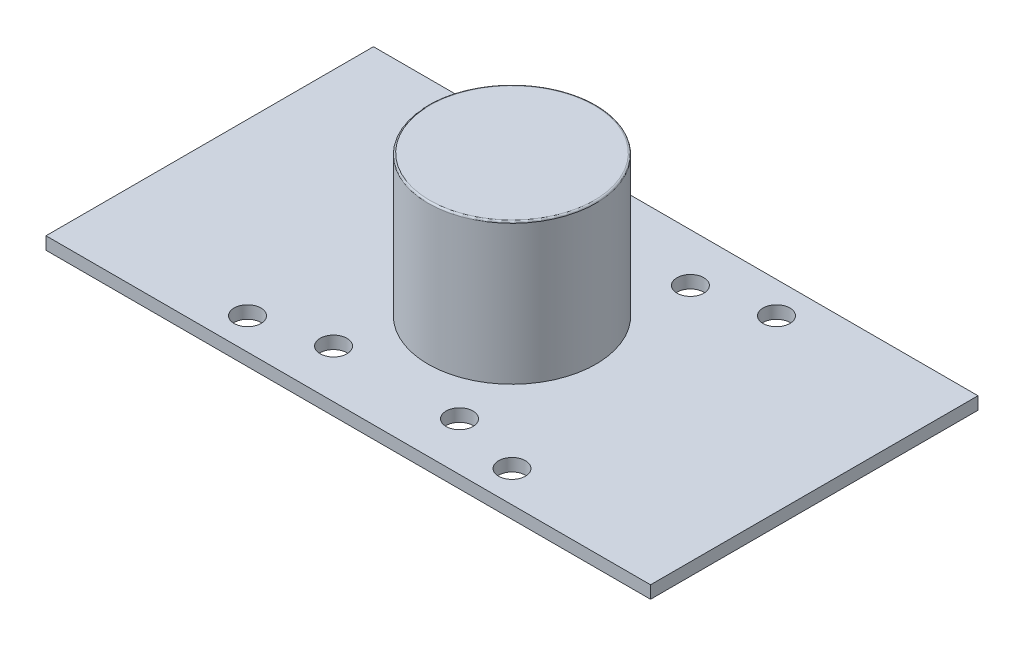
SolidWorks part; units mm, degrees
ref_plane "Front Plane" through (0, 0, 0) normal (0, 0, 1) x (1, 0, 0)
ref_plane "Top Plane" through (0, 0, 0) normal (0, 1, 0) x (1, 0, 0)
ref_plane "Right Plane" through (0, 0, 0) normal (1, 0, 0) x (0, 0, -1)
sketch "Sketch1" plane through (0, 0, 0) normal (0, 1, 0) x (1, 0, 0)
  line L0 (0, 0) -> (72, 0)
  line L1 (72, 0) -> (72, 39)
  line L2 (72, 39) -> (0, 39)
  line L3 (0, 39) -> (0, 0)
extrude "Boss-Extrude1" add sketch "Sketch1" along normal blind 1.5
sketch "Sketch2" plane through (0, 1.5, 0) normal (0, 1, 0) x (1, 0, 0)
  circle A0 centre (36, 19.5) radius 10
extrude "Boss-Extrude2" add sketch "Sketch2" along normal blind 16.8
sketch "Sketch3" plane through (0, 1.5, 0) normal (0, 1, 0) x (1, 0, 0)
  circle A0 centre (43.5, 5.75) radius 1.6
  circle A1 centre (28.5, 5.75) radius 1.6
  circle A2 centre (28.5, 33.25) radius 1.6
  circle A3 centre (43.5, 33.25) radius 1.6
extrude "Cut-Extrude1" cut sketch "Sketch3" against normal blind 16.8
sketch "Sketch4" plane through (0, 1.5, 0) normal (0, 1, 0) x (1, 0, 0)
  circle A0 centre (51.75, 3.75) radius 1.6
  circle A1 centre (51.75, 35.25) radius 1.6
  circle A2 centre (20.25, 3.75) radius 1.6
  circle A3 centre (20.25, 35.25) radius 1.6
extrude "Cut-Extrude2" cut sketch "Sketch4" against normal blind 16.8
fillet "Fillet1" radius 0.2 1 edges at (36, 18.3, -9.5)
